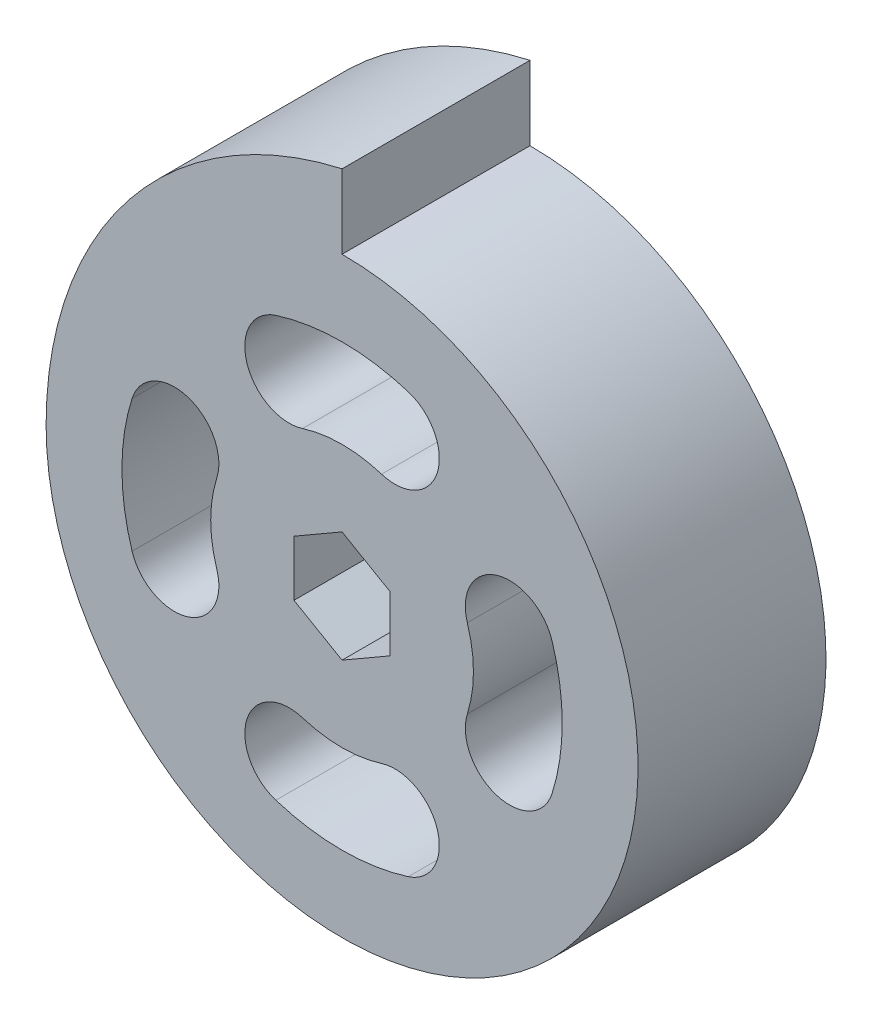
SolidWorks part; units mm, degrees
material "AR500"
ref_plane "Front Plane" through (0, 0, 0) normal (0, 0, 1) x (1, 0, 0)
ref_plane "Top Plane" through (0, 0, 0) normal (0, 1, 0) x (1, 0, 0)
ref_plane "Right Plane" through (0, 0, 0) normal (1, 0, 0) x (0, 0, -1)
sketch "Sketch3" plane through (0, 0, 0) normal (0, 0, 1) x (1, 0, 0)
  line L5 (0, 20) -> (0, 25)
  line L6 (3.25, -1.8764) -> (3.25, 1.8764)
  line L7 (3.25, 1.8764) -> (0, 3.7528)
  line L8 (0, 3.7528) -> (-3.25, 1.8764)
  line L9 (-3.25, 1.8764) -> (-3.25, -1.8764)
  line L10 (-3.25, -1.8764) -> (0, -3.7528)
  line L11 (0, -3.7528) -> (3.25, -1.8764)
  circle A2 centre (0, 0) radius 20 construction
  circle A3 centre (0, 0) radius 3.25 construction
  arc A9 (0, 25) -> (-20, 0) centre (5.625, 0) ccw
  arc A10 (0, 20) -> (-20, 0) centre (0, 0) cw
  point P3 (0, 0)
  point P25 (0, 0)
  dimension "D2" = 5
  dimension "D1" = 40
  dimension "D3" = 6.5
extrude "Boss-Extrude1" add sketch "Sketch3" along normal blind 12.7
sketch "Sketch4" plane through (0, 0, 12.7) normal (0, 0, 1) x (1, 0, 0)
  line L0 (0, 20) -> (0, 3.7528) construction
  line L1 (-3.5713, 11.3267) -> (0, 0) construction
  line L2 (0, 0) -> (3.5713, 11.3267) construction
  circle A0 centre (0, 0) radius 11.8764 construction
  circle A2 centre (-3.5713, 11.3267) radius 3 construction
  circle A3 centre (3.5713, 11.3267) radius 3 construction
  arc A4 (-4.4734, 14.1879) -> (4.4734, 14.1879) centre (0, 0) cw
  arc A5 (2.6692, 8.4656) -> (-2.6692, 8.4656) centre (0, 0) ccw
  circle A6 centre (0, 11.8764) radius 3 construction
  arc A7 (-4.4734, 14.1879) -> (-2.6692, 8.4656) centre (-3.5713, 11.3267) ccw
  arc A8 (2.6692, 8.4656) -> (4.4734, 14.1879) centre (3.5713, 11.3267) ccw
  point P5 (0, 11.8764)
  point P7 (0, 20)
  dimension "D2" = 3
  dimension "D1" = 35
extrude "Cut-Extrude1" cut sketch "Sketch4" against normal through all
ref_axis "Axis1" through (0, 0, -0.475) along (0, 0, 1)
pattern_circular "CirPattern1" count 4 over 360 about axis through (0, 0, -0.475) along (0, 0, 1) of "Cut-Extrude1"
